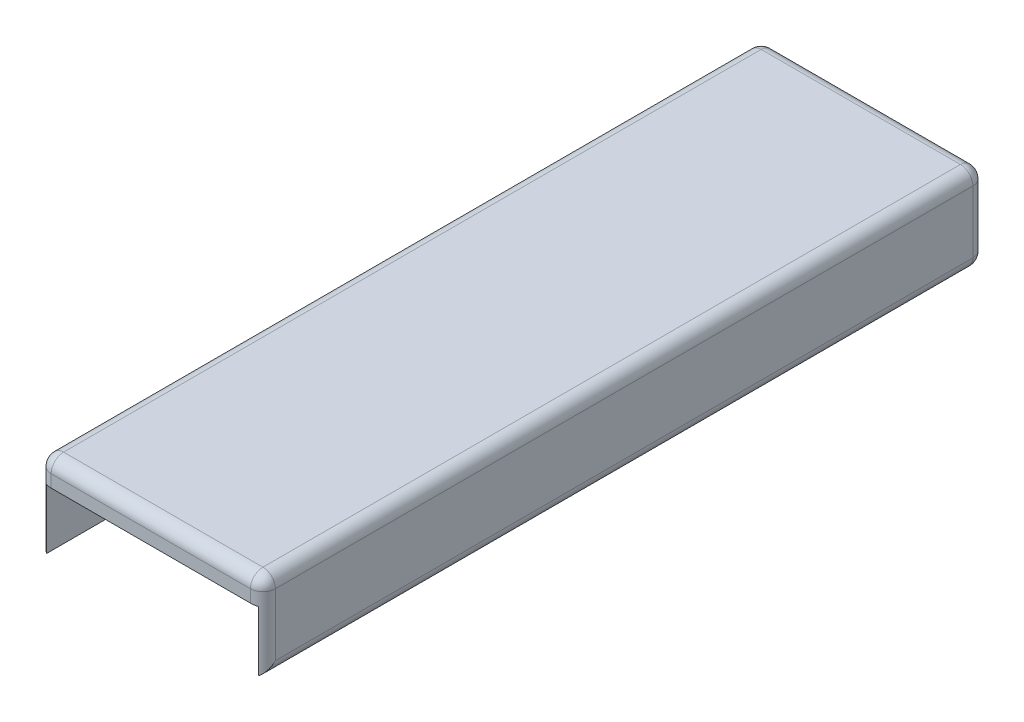
SolidWorks part; units mm, degrees
ref_plane "Front Plane" through (0, 0, 0) normal (0, 0, 1) x (1, 0, 0)
ref_plane "Top Plane" through (0, 0, 0) normal (0, 1, 0) x (1, 0, 0)
ref_plane "Right Plane" through (0, 0, 0) normal (1, 0, 0) x (0, 0, -1)
sketch "Sketch1" plane through (0, 0, 0) normal (0, 1, 0) x (1, 0, 0)
  line L1 (-9, -29) -> (9, -29)
  line L2 (-9, -29) -> (-9, 29)
  line L3 (-9, 29) -> (9, 29)
  line L4 (9, -29) -> (9, 29)
  line L5 (-9, -29) -> (9, 29) construction
  line L6 (-9, 29) -> (9, -29) construction
  point P0 (0, 0)
  dimension "D1" = 58
  dimension "D2" = 18
extrude "Boss-Extrude1" add sketch "Sketch1" along normal mid plane 7
sketch "Sketch2" plane through (0, -3.5, 0) normal (0, -1, 0) x (1, 0, 0)
  line L0 (-9, 29) -> (9, 29) construction
  line L1 (-8.5, 29) -> (8.5, 29)
  line L2 (-8.5, 29) -> (-8.5, 22)
  line L3 (-8.5, 22) -> (8.5, 22)
  line L4 (8.5, 29) -> (8.5, 22)
  line L5 (-8.5, 29) -> (-9, 29) construction
  line L7 (9, 29) -> (8.5, 29) construction
  dimension "D1" = 0.5
  dimension "D2" = 7
extrude "Cut-Extrude1" cut sketch "Sketch2" against normal offset from surface 2 up to face at (0, 3.5, 0)
chamfer "Chamfer1" distance 7 distance2 3 1 edges at (0, 1.5, 22) first distance on face at (0, 1.5, 25.5)
fillet "Fillet2" radius 1 11 edges at (0, -3.5, -29) (-9, 0, -29) (-9, -3.5, 0) (0, 3.5, -29) (-9, 3.5, 0) (9, 0, -29) (9, -3.5, 0) (9, 3.5, 0) (-9, 0, 29) (0, 3.5, 29) (9, 0, 29)
sketch "Sketch3" plane through (0, 0, 22) normal (0, 0, 1) x (1, 0, 0)
  line L0 (-8, -3.5) -> (8, -3.5) construction
  line L1 (0, -3.5) -> (-8.5, -3.5)
  line L2 (0, -3.5) -> (0, -0.0287)
  line L3 (0, -0.0287) -> (-8.5, -0.0287)
  line L4 (-8.5, -3.5) -> (-8.5, -0.0287)
  line L5 (-8.5, -1.5) -> (-8.5, 1.4426) construction
extrude "Boss-Extrude2" add sketch "Sketch3" along normal blind 0.1
